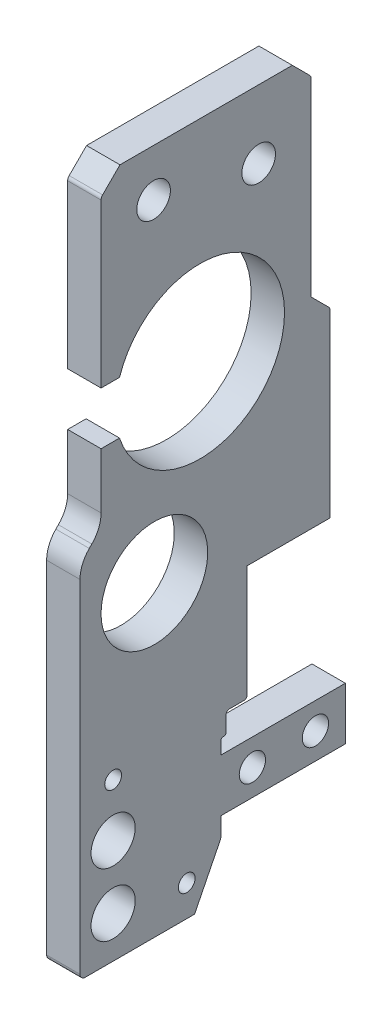
SolidWorks part; units mm, degrees
material "6061 Alloy"
ref_plane "Front Plane" through (0, 0, 0) normal (0, 0, 1) x (1, 0, 0)
ref_plane "Top Plane" through (0, 0, 0) normal (0, 1, 0) x (1, 0, 0)
ref_plane "Right Plane" through (0, 0, 0) normal (1, 0, 0) x (0, 0, -1)
sketch "Sketch1" plane through (0, 0, 0) normal (1, 0, 0) x (0, 0, -1)
  line L2 (0, 0) -> (0, 34.275)
  line L3 (0, 34.275) -> (2, 36.275)
  line L4 (2, 36.275) -> (2, 65.31)
  line L5 (2, 65.31) -> (22, 65.31)
  line L7 (23.8, 26.21) -> (15.9, 26.21)
  line L8 (13.4, 13.26) -> (13.4, 11.86)
  line L9 (13.4, 11.86) -> (25.25, 11.86)
  line L10 (25.25, 11.86) -> (25.25, 6.86)
  line L11 (25.25, 6.86) -> (13.4, 6.86)
  line L12 (13.4, 6.86) -> (13.4, 0)
  line L13 (13.4, 0) -> (0, 0)
  line L14 (-6.9356, -4) -> (62.4069, -4) construction
  line L15 (7.075, 34.275) -> (0, 34.275) construction
  line L16 (7.075, 24.125) -> (0, 24.125) construction
  line L17 (2, 22.125) -> (2, 36.275) construction
  line L18 (13.4, 13.26) -> (13.9, 13.26)
  line L19 (15.9, 15.26) -> (15.9, 26.21)
  line L23 (22, 65.31) -> (22, 45.31)
  line L24 (22, 45.31) -> (23.8, 45.31)
  line L25 (23.8, 45.31) -> (23.8, 26.21)
  line L29 (15.9, 15.26) -> (13.9, 15.26)
  line L30 (13.9, 13.26) -> (13.9, 15.26)
  circle A0 centre (7.075, 29.2) radius 5.075
  circle A1 centre (7, 60.81) radius 1.6
  circle A2 centre (17, 58.81) radius 1.6
  circle A3 centre (22.4, 9.36) radius 1.25
  circle A4 centre (16.4, 9.36) radius 1.25
  circle A5 centre (3.15, 3.95) radius 2.1
  circle A6 centre (3.15, 9.95) radius 2.1
  circle A7 centre (22.4, 9.36) radius 2.85 construction
  circle A8 centre (16.4, 9.36) radius 2.85 construction
  circle A9 centre (10.15, 2.95) radius 0.8
  circle A10 centre (3.15, 14.95) radius 0.8
  dimension "D11" = 10.15
  dimension "D13" = 3.2
  dimension "D17" = 5
  dimension "D21" = 2.5
  dimension "D29" = 7.9
  dimension "D33" = 4.2
  dimension "D34" = 5.7
  dimension "D35" = 2
  dimension "D36" = 1.6
  dimension "D3" = 10.86
  dimension "D4" = 5
  dimension "D5" = 14.35
  dimension "D6" = 11.85
  dimension "D7" = 65.31
  dimension "D8" = 4
  dimension "D9" = 2
  dimension "D10" = 2
  dimension "D12" = 33.2
  dimension "D14" = 6.5
  dimension "D15" = 4.5
  dimension "D16" = 5
  dimension "D18" = 6
  dimension "D19" = 1.45
  dimension "D20" = 2.5
  dimension "D22" = 1.4
  dimension "D23" = 7
  dimension "D24" = 20
  dimension "D25" = 2.95
  dimension "D26" = 1.8
  dimension "D27" = 20
  dimension "D28" = 2
  dimension "D30" = 6
  dimension "D31" = 3.95
  dimension "D32" = 3.15
  dimension "D38" = 12
extrude "Boss-Extrude1" add sketch "Sketch1" along normal blind 3.18
chamfer "Chamfer1" distance 2.5 angle 63.43 1 edges at (1.59, 0, -13.4) first distance on face at (1.59, 0, -6.7)
fillet "Fillet1" [suppressed] radius 1
sketch "Sketch3" [suppressed] plane through (0, 0, 0) normal (1, 0, 0) x (0, 0, -1)
  line L1 (-17.4326, 42.2448) -> (-6.9749, 46.4147) construction
  line L2 (-6.9749, 46.4147) -> (-8.5925, 35.2732) construction
  line L3 (-8.5925, 35.2732) -> (-17.4326, 42.2448) construction
  line L4 (-2, 61.31) -> (-2, 32.2) construction
  circle A0 centre (-11, 41.3109) radius 5
  circle A2 centre (-11, 41.3109) radius 6.5 construction
  circle A3 centre (-6.9749, 46.4147) radius 1.2 construction
  circle A4 centre (-8.5925, 35.2732) radius 1.2 construction
  circle A5 centre (-17.4326, 42.2448) radius 1.2 construction
  circle A6 centre (-7, 25.2) radius 5 construction
  dimension "D1" = 10
  dimension "D3" = 16.6
  dimension "D4" = 13
  dimension "D5" = 2.4
  dimension "D2" = 9
hole_wizard "CSK for M2 Flat Head Machine Screw1" [suppressed] positions "Sketch6" profile "Sketch7" countersink size "M2" standard "ANSI Metric"
sketch "Sketch6" plane through (0, 0, 0) normal (-1, 0, 0) x (0, 0, 1)
  point P0 (-6.9749, 46.4147)
  point P3 (-17.4326, 42.2448)
  point P6 (-8.5925, 35.2732)
sketch "Sketch7" plane through (0, 46.4147, -6.9749) normal (0, 1, 0) x (0, 0, 1)
  line L0 (0, 0) -> (0, 4.23)
  line L1 (0, 4.23) -> (1.2, 3.509)
  line L2 (1.2, 3.509) -> (1.2, 1)
  line L3 (1.2, 1) -> (2.2, 0)
  line L5 (2.2, 0) -> (0, 0)
  line L6 (-1.2, 1) -> (-2.2, 0) construction
  line L10 (0, 4.23) -> (-1.2, 3.509) construction
  line L11 (0, -6.35) -> (0, 107.95) construction
  dimension "Hole Dia." = 2.4
  dimension "Hole Depth" = 4.23
  dimension "Near C'Sink Dia." = 4.4
  dimension "Near C'Sink Angle" = 90
  dimension "Drill Angle" = 118
extrude "Cut-Extrude4" [suppressed] cut sketch "Sketch3" against normal through all
fillet "Fillet2" radius 3 2 edges at (1.59, 34.275, 0) (1.59, 36.275, -2)
fillet "Chamfer2" radius 1.8 3 edges at (1.59, 65.31, -22) (1.59, 65.31, -2) (1.59, 45.31, -23.8) profile chamfer
fillet "Fillet4" radius 0.5 5 edges at (1.59, 63.51, -2) (1.59, 63.51, -22) (1.59, 43.51, -23.8) (1.59, 0, 0) (1.59, 4.9989, -13.4)
fillet "Fillet6" [suppressed] radius 0.3
sketch "BallRef" [suppressed] plane through (0, 0, 0) normal (-1, 0, 0) x (0, 0, 1)
  line L0 (-31.524, -18.06) -> (65.6624, -18.06) construction
  line L1 (-0.75, 25.2) -> (-0.75, 21.8885) construction
  line L2 (-0.75, 21.8885) -> (31.3703, 21.8885) construction
  line L3 (31.3703, 3.35) -> (31.3703, 21.8885) construction
  line L4 (1.092, -18.06) -> (-13.908, -3.06) construction
  line L5 (-13.908, -3.06) -> (-13.908, -18.06) construction
  line L6 (-13.908, -18.06) -> (1.092, -18.06) construction
  circle A0 centre (-7, 25.2) radius 6.25 construction
  circle A1 centre (9.9603, 3.35) radius 21.41 construction
  dimension "D1" = 12.5
  dimension "D2" = 42.82
  dimension "D3" = 43.26
  dimension "D4" = 45
  dimension "D5" = 15
fillet "Fillet7" radius 0.2 2 edges at (1.59, 13.26, -13.4) (1.59, 13.26, -13.9)
hole_wizard "M3x0.5 Tapped Hole1" positions "Sketch9" profile "Sketch10" tap size "M3x0.5" standard "ANSI Metric" end condition through all
sketch "Sketch9" plane through (3.18, 0, 0) normal (1, 0, 0) x (0, 0, -1)
  point P0 (16.4, 9.36)
  point P3 (22.4, 9.36)
sketch "Sketch10" plane through (3.18, 9.36, -16.4) normal (0, 1, 0) x (0, 0, -1)
  line L0 (0, 0) -> (0, 3.18)
  line L1 (0, 3.18) -> (1.25, 3.18)
  line L2 (1.25, 3.18) -> (1.25, 0)
  line L5 (1.25, 0) -> (0, 0)
  line L11 (0, -6.35) -> (0, 107.95) construction
  dimension "Thru Tap Drill Dia." = 2.5
  dimension "Thru Tap Drill Depth" = 3.18
hole_wizard "M2 Tapped Hole1" positions "3DSketch1" profile "Sketch12" tap size "M2" standard "AS" end condition through all
sketch3d "3DSketch1"
  line L0 (3.18, 14.95, -3.15) -> (0, 14.95, -3.15) construction
  line L1 (3.18, 2.95, -10.15) -> (0, 2.95, -10.15) construction
  point P0 (0, 14.95, -3.15)
  point P4 (0, 2.95, -10.15)
sketch "Sketch12" plane through (0, 14.95, -3.15) normal (0, 1, 0) x (0, 0, 1)
  line L0 (0, 0) -> (0, 3.18)
  line L1 (0, 3.18) -> (0.8, 3.18)
  line L2 (0.8, 3.18) -> (0.8, 0)
  line L5 (0.8, 0) -> (0, 0)
  line L11 (0, -6.35) -> (0, 107.95) construction
  dimension "Thru Tap Drill Dia." = 1.6
  dimension "Thru Tap Drill Depth" = 3.18
cosmetic thread "Hole Thread3" parameters "D2"=2
cosmetic thread "Hole Thread4" parameters "D2"=2
fillet "Fillet8" radius 0.3 2 edges at (1.59, 15.26, -15.9) (1.59, 15.26, -13.9)
sketch "Sketch13" plane through (3.18, 0, 0) normal (1, 0, 0) x (0, 0, -1)
  line L9 (11.4101, 65.31) -> (11.4101, 0) construction
  line L10 (20.2, 65.31) -> (3.8, 65.31) construction
  line L11 (0.5, 0) -> (10.9, 0) construction
  line L12 (2, 63.3029) -> (2, 37.5176) construction
  line L13 (2, 42.81) -> (24.5, 42.81) construction
  line L14 (23.6536, 43.6564) -> (22, 45.31) construction
  line L15 (2, 42.81) -> (3.7581, 42.81)
  line L16 (2, 42.81) -> (2, 47.81)
  line L17 (2, 47.81) -> (3.7581, 47.81)
  arc A1 (3.7581, 42.81) -> (3.7581, 47.81) centre (11.4101, 45.31) ccw
  dimension "D3" = 16.1
  dimension "D1" = 9.4101
  dimension "D2" = 45.31
  dimension "D4" = 2.5
extrude "Cut-Extrude5" cut sketch "Sketch13" against normal blind 4
equation "\"7.5.00mm\"=5"
